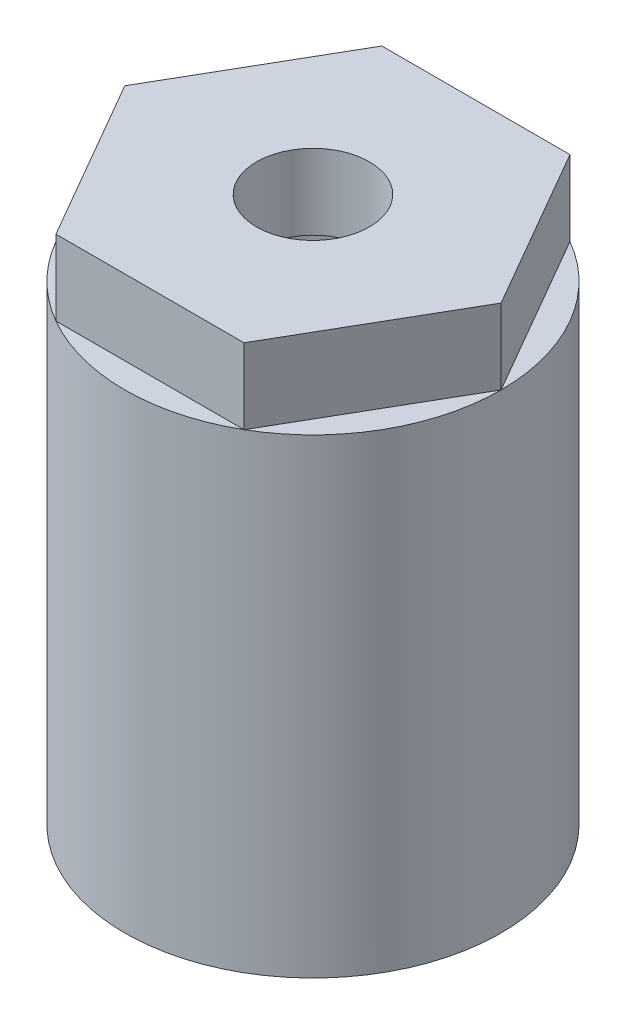
SolidWorks part; units mm, degrees
material "6061-T6 (SS)"
ref_plane "Piano frontale" through (0, 0, 0) normal (0, 0, 1) x (1, 0, 0)
ref_plane "Piano superiore" through (0, 0, 0) normal (0, 1, 0) x (1, 0, 0)
ref_plane "Piano destro" through (0, 0, 0) normal (1, 0, 0) x (0, 0, -1)
sketch "Schizzo1" plane through (0, 0, 0) normal (0, 0, 1) x (1, 0, 0)
  line L0 (0, 0) -> (0, 23.6846) construction
  line L1 (-14, 0) -> (-14, 38)
  line L2 (-14, 38) -> (0, 38)
  line L3 (0, 38) -> (0, 46)
  line L4 (0, 46) -> (-20, 46)
  line L5 (-20, 46) -> (-20, 0)
  line L6 (-20, 0) -> (-14, 0)
  line L7 (-20, 0) -> (-20, -12)
  line L8 (-20, -12) -> (-18, -12)
  line L9 (-18, 0) -> (-18, -12) construction
  line L10 (-18, -12) -> (-18, 0)
  line L11 (-18, 0) -> (-18, -12) construction
  line L12 (-15, 0) -> (-15, 5)
  line L13 (-15, 5) -> (-14, 6)
  dimension "D1" = 28
  dimension "D2" = 40
  dimension "D3" = 8
  dimension "D4" = 38
  dimension "D5" = 12
  dimension "D6" = 1
  dimension "D7" = 5
  dimension "D8" = 45
revolve "Rivoluzione1" add sketch "Schizzo1" angle 360 about L0 region at (-14.1081, 28.8545, 0) region at (-19, -6, 0)
sketch "Schizzo2" plane through (0, 46, 0) normal (0, 1, 0) x (1, 0, 0)
  circle A0 centre (0, 0) radius 6
  dimension "D1" = 12
extrude "Taglio-Estrusione1" cut sketch "Schizzo2" against normal blind 11
ref_plane "Piano1" through (0, 0, -20) normal (0, 0, -1) x (-1, 0, 0)
sketch "Schizzo3" plane through (0, 0, -20) normal (0, 0, -1) x (-1, 0, 0)
  circle A0 centre (0, 26) radius 0.5
  circle A1 centre (0, 4) radius 1.5
  dimension "D1" = 1
  dimension "D3" = 3
  dimension "D2" = 26
  dimension "D4" = 4
extrude "Taglio-Estrusione2" cut sketch "Schizzo3" against normal blind 10
sketch "Schizzo4" plane through (0, 46, 0) normal (0, 1, 0) x (1, 0, 0)
  line L0 (-10, 17.3205) -> (-20, 0)
  line L1 (-20, 0) -> (-10, -17.3205)
  line L2 (-10, -17.3205) -> (10, -17.3205)
  line L3 (10, -17.3205) -> (20, 0)
  line L4 (20, 0) -> (10, 17.3205)
  line L5 (10, 17.3205) -> (-10, 17.3205)
  circle A0 centre (0, 0) radius 20 construction
  circle A3 centre (0, 0) radius 20
  circle M9 centre (0, 0) radius 20
fillet "Raccordo1" radius 0.5 1 edges at (0, 38, -14)
extrude "Taglio-Estrusione3" cut sketch "Schizzo4" against normal blind 8 contours L0 M9 | L1 M9 | L2 M9 | L3 M9 | L4 M9 | L5 M9 region at (0, 46, -18.3987) region at (-15.9337, 46, -9.1994) region at (-15.9337, 46, 9.1994) region at (15.9337, 46, -9.1994) region at (0, 46, 18.3987) region at (15.9337, 46, 9.1994)
